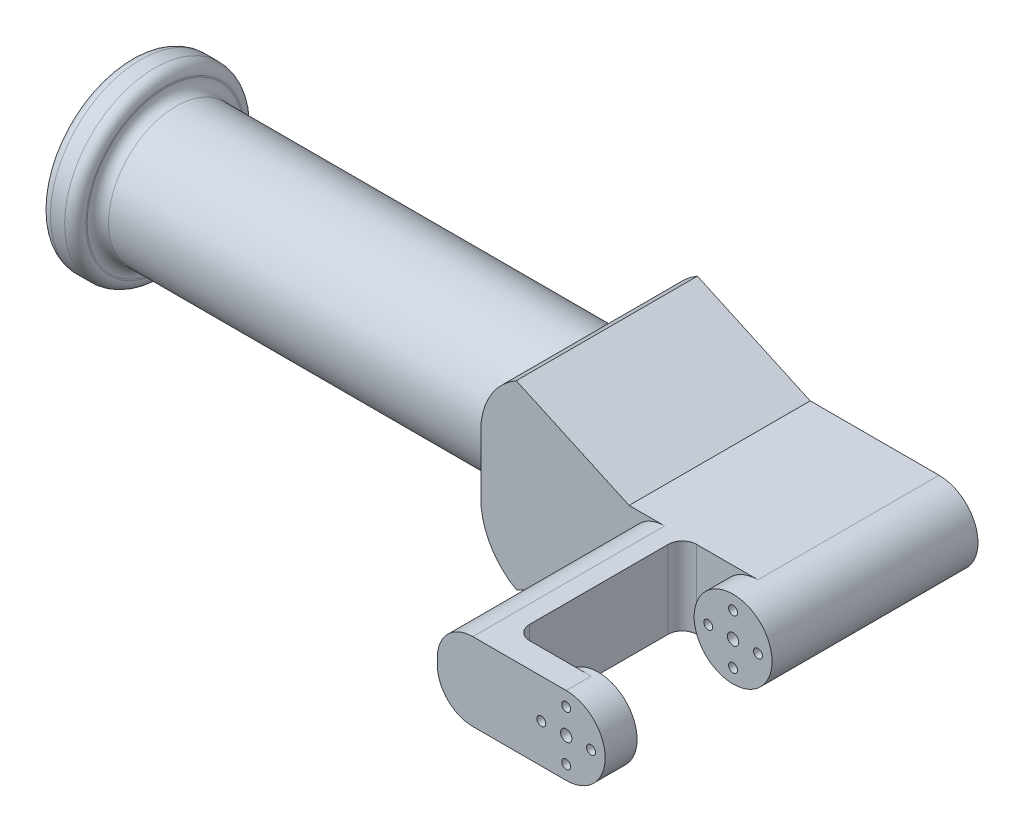
SolidWorks part; units mm, degrees
material "PET"
ref_plane "Front Plane" through (0, 0, 0) normal (0, 0, 1) x (1, 0, 0)
ref_plane "Top Plane" through (0, 0, 0) normal (0, 1, 0) x (1, 0, 0)
ref_plane "Right Plane" through (0, 0, 0) normal (1, 0, 0) x (0, 0, -1)
sketch "Sketch1" plane through (0, 0, 0) normal (1, 0, 0) x (0, 0, -1)
  line L0 (0, 10.97) -> (80, 10.97)
  line L1 (80, 10.97) -> (80, -10.97)
  line L2 (0, -10.97) -> (80, -10.97)
  arc A0 (0, 10.97) -> (0, -10.97) centre (0, 0) ccw
  dimension "D1" = 21.94
  dimension "D2" = 80
extrude "Boss-Extrude1" add sketch "Sketch1" along normal blind 15
sketch "Sketch2" plane through (15, 0, 0) normal (1, 0, 0) x (0, 0, -1)
  line L0 (0, 28.05) -> (0, -28.05) construction
  circle A0 centre (0, 0) radius 10.97
  circle A1 centre (0, 0) radius 1.6
  circle A2 centre (0, 6.58) radius 1.25
  circle A3 centre (6.58, 0) radius 1.25
  circle A4 centre (0, -6.58) radius 1.25
  circle A5 centre (-6.58, 0) radius 1.25
  point P17 (0, 0)
  dimension "D1" = 3.2
  dimension "D2" = 2.5
  dimension "D3" = 6.58
  dimension "D4" = 4
extrude "Boss-Extrude2" add sketch "Sketch2" along normal blind 5.89
sketch "Sketch3" plane through (20.89, 0, 0) normal (1, 0, 0) x (0, 0, -1)
  circle A0 centre (0, 6.58) radius 1.25
  circle A1 centre (0, 0) radius 1.6
  circle A2 centre (0, -6.58) radius 1.25
  circle A3 centre (-6.58, 0) radius 1.25
  circle A4 centre (6.58, 0) radius 1.25
extrude "Cut-Extrude1" cut sketch "Sketch3" against normal blind 100
sketch "Sketch4" plane through (15, 0, 0) normal (1, 0, 0) x (0, 0, -1)
  line L0 (80, 10.97) -> (0, 10.97) construction
  line L1 (30, 10.97) -> (80, 10.97)
  line L2 (30, 10.97) -> (30, -10.97)
  line L3 (30, -10.97) -> (80, -10.97)
  line L4 (80, 10.97) -> (80, -10.97)
  dimension "D1" = 30
extrude "Boss-Extrude3" add sketch "Sketch4" along normal blind 49.02
sketch "Sketch5" plane through (0, 0, 0) normal (0, 1, 0) x (1, 0, 0)
  line L0 (0, -12.067) -> (0, 12.067) construction
  line L1 (64.02, 34.7595) -> (0, 34.7595) construction
  line L2 (64.02, 80) -> (64.02, 30) construction
  line L3 (32.01, 80) -> (32.01, -10.8477) construction
  line L4 (64.02, 80) -> (0, 80) construction
sketch "Sketch6" plane through (0, 10.97, 0) normal (0, 1, 0) x (1, 0, 0)
  line L0 (64.02, 80) -> (0, 80) construction
  line L1 (15, 30) -> (44, 30)
  line L2 (15, 30) -> (15, 80)
  line L3 (15, 80) -> (44, 80)
  line L4 (44, 30) -> (44, 80)
sketch "Sketch9" plane through (0, 0, 0) normal (-1, 0, 0) x (0, 0, 1)
  line L0 (-80, 0) -> (10.8477, 0) construction
  line L1 (-80, 25.5) -> (-29, 25.5)
  line L2 (-80, 25.5) -> (-80, -25.5)
  line L3 (-80, -25.5) -> (-29, -25.5)
  line L4 (-29, 25.5) -> (-29, -25.5)
  line L5 (-80, 25.5) -> (-29, -25.5) construction
  line L6 (-80, -25.5) -> (-29, 25.5) construction
  line L7 (-80, 10.97) -> (-80, -10.97) construction
  point P0 (-54.5, 0)
  dimension "D1" = 29
  dimension "D2" = 25.5
  dimension "D3" = 0
extrude "Boss-Extrude7" add sketch "Sketch9" along normal blind 10
sketch "Sketch10" plane through (-10, 0, 0) normal (-1, 0, 0) x (0, 0, 1)
  line L0 (-80, 0) -> (-29, 0) construction
  line L1 (-80, 10.97) -> (-80, -10.97) construction
  line L2 (-29, -25.5) -> (-29, 25.5) construction
  circle A0 centre (-54.5, 0) radius 19.05
  dimension "D1" = 38.1
extrude "Boss-Extrude8" add sketch "Sketch10" along normal blind 114.3
sketch "Sketch11" plane through (-124.3, 0, 0) normal (-1, 0, 0) x (0, 0, 1)
  line L0 (-73.55, 0) -> (-35.45, 0) construction
  line L1 (-80, 0) -> (10.8477, 0) construction
  circle A0 centre (-54.5, 0) radius 19.05 construction
  circle A1 centre (-54.5, 0) radius 25.4
  dimension "D1" = 50.8
extrude "Boss-Extrude9" add sketch "Sketch11" along normal blind 10
sketch "Sketch12" plane through (0, 0, -30) normal (0, 0, 1) x (1, 0, 0)
  line L0 (64.02, -10.97) -> (15, -10.97) construction
  line L1 (64.02, 10.97) -> (49.02, 10.97)
  line L2 (64.02, 10.97) -> (64.02, -10.97)
  line L3 (64.02, -10.97) -> (49.02, -10.97)
  line L4 (49.02, 10.97) -> (49.02, -10.97)
  dimension "D1" = 15
extrude "Boss-Extrude10" add sketch "Sketch12" along normal blind 30
sketch "Sketch13" plane through (64.02, 0, 0) normal (1, 0, 0) x (0, 0, -1)
  circle A0 centre (0, 0) radius 10.97
  circle A1 centre (0, 0) radius 1.6
  circle A2 centre (6.58, 0) radius 1.25
  circle A3 centre (0, 6.58) radius 1.25
  circle A4 centre (0, -6.58) radius 1.25
  circle A5 centre (-6.58, 0) radius 1.25
  point P17 (0, 0)
  dimension "D1" = 4
extrude "Boss-Extrude11" add sketch "Sketch13" against normal blind 20.89
sketch "Sketch15" plane through (64.02, 0, 0) normal (1, 0, 0) x (0, 0, -1)
  circle A0 centre (0, 0) radius 1.6
  circle A1 centre (0, 6.58) radius 1.25
  circle A2 centre (6.58, 0) radius 1.25
  circle A3 centre (0, -6.58) radius 1.25
  circle A4 centre (-6.58, 0) radius 1.25
  point P15 (0, 0)
  dimension "D1" = 4
extrude "Cut-Extrude2" cut sketch "Sketch15" against normal blind 20.89
sketch "Sketch17" plane through (0, 0, 0) normal (1, 0, 0) x (0, 0, -1)
  line L1 (29, 25.5) -> (80, 25.5)
  line L2 (29, 25.5) -> (29, -25.5)
  line L3 (29, -25.5) -> (80, -25.5)
  line L4 (80, 25.5) -> (80, -25.5)
extrude "Boss-Extrude12" add sketch "Sketch17" along normal blind 79.02
sketch "Sketch18" plane through (0, 0, -29) normal (0, 0, 1) x (1, 0, 0)
  line L1 (39.5513, 13.4042) -> (70.044, 13.4042)
  line L2 (39.5513, 13.4042) -> (39.5513, -17.0884)
  line L3 (39.5513, -17.0884) -> (70.044, -17.0884)
  line L4 (70.044, 13.4042) -> (70.044, -17.0884)
extrude "Cut-Extrude3" cut sketch "Sketch18" along normal blind 64
sketch "Sketch19" plane through (0, 0, -29) normal (0, 0, 1) x (1, 0, 0)
  line L0 (79.02, 25.5) -> (79.02, -25.5) construction
  line L1 (79.02, 10.97) -> (64.02, 10.97)
  line L2 (79.02, 10.97) -> (79.02, -10.97)
  line L3 (79.02, -10.97) -> (64.02, -10.97)
  line L4 (64.02, 10.97) -> (64.02, -10.97)
  line L5 (50.0335, 0) -> (-50.0335, 0) construction
  dimension "D1" = 15
  dimension "D2" = 21.94
  dimension "D3" = 10.97
extrude "Boss-Extrude13" add sketch "Sketch19" along normal blind 29
sketch "Sketch20" plane through (79.02, 0, 0) normal (1, 0, 0) x (0, 0, -1)
  circle A0 centre (0, 0) radius 10.97
  circle A1 centre (0, 0) radius 1.6
  circle A2 centre (0, 6.58) radius 1.25
  circle A3 centre (6.58, 0) radius 1.25
  circle A4 centre (0, -6.58) radius 1.25
  circle A5 centre (-6.58, 0) radius 1.25
  point P17 (0, 0)
  dimension "D1" = 4
extrude "Boss-Extrude14" add sketch "Sketch20" against normal blind 20.98
sketch "Sketch21" plane through (79.02, 0, 0) normal (1, 0, 0) x (0, 0, -1)
  circle A0 centre (0, 0) radius 1.6
  circle A1 centre (0, 6.58) radius 1.25
  circle A2 centre (6.58, 0) radius 1.25
  circle A3 centre (0, -6.58) radius 1.25
  circle A4 centre (-6.58, 0) radius 1.25
  point P14 (0, 0)
  dimension "D1" = 4
extrude "Cut-Extrude4" cut sketch "Sketch21" against normal blind 20.98
sketch "Sketch23" plane through (79.02, 0, 0) normal (1, 0, 0) x (0, 0, -1)
  line L0 (29, -10.97) -> (29, -25.5) construction
  line L1 (-13.4821, 15.5896) -> (29, 15.5896)
  line L2 (-13.4821, 15.5896) -> (-13.4821, -18.235)
  line L3 (-13.4821, -18.235) -> (29, -18.235)
  line L4 (29, 15.5896) -> (29, -18.235)
extrude "Cut-Extrude6" cut sketch "Sketch23" against normal blind 100
sketch "Sketch27" plane through (0, 0, -29) normal (0, 0, 1) x (1, 0, 0)
  line L1 (44, 0) -> (-44, 0) construction
  line L2 (25.67, 18.75) -> (52.37, 18.75)
  line L3 (25.67, 18.75) -> (25.67, -18.75)
  line L4 (25.67, -18.75) -> (52.37, -18.75)
  line L5 (52.37, 18.75) -> (52.37, -18.75)
  line L6 (25.67, 18.75) -> (52.37, -18.75) construction
  line L7 (25.67, -18.75) -> (52.37, 18.75) construction
  line L8 (79.02, 25.5) -> (79.02, -25.5) construction
  point P2 (39.02, 0)
  dimension "D1" = 26.7
  dimension "D2" = 37.5
  dimension "D3" = 40
sketch "Sketch24" plane through (0, 25.5, 0) normal (0, 1, 0) x (1, 0, 0)
  line L0 (-10, 54.5) -> (79.02, 54.5) construction
  line L1 (-10, 29) -> (-10, 80) construction
  line L2 (79.02, 80) -> (79.02, 29) construction
  circle A0 centre (34.51, 54.5) radius 1.6
  circle A1 centre (34.51, 61.08) radius 1.25
  circle A2 centre (41.09, 54.5) radius 1.25
  circle A3 centre (34.51, 47.92) radius 1.25
  circle A4 centre (27.93, 54.5) radius 1.25
  dimension "D1" = 3.2
  dimension "D2" = 2.5
  dimension "D3" = 6.58
  dimension "D4" = 4
sketch "Sketch31" plane through (0, 25.5, 0) normal (0, 1, 0) x (1, 0, 0)
  line L0 (-28.05, 0) -> (28.05, 0) construction
  line L1 (-10, 80) -> (40.8, 80)
  line L2 (-10, 80) -> (-10, 0)
  line L3 (-10, 0) -> (40.8, 0)
  line L4 (40.8, 80) -> (40.8, 0)
  dimension "D1" = 50.8
sketch "Sketch32" plane through (0, 25.5, 0) normal (0, 1, 0) x (1, 0, 0)
  line L0 (-10, 80) -> (79.02, 80) construction
  line L1 (79.02, 29) -> (40.8, 29)
  line L2 (79.02, 29) -> (79.02, 80)
  line L3 (79.02, 80) -> (40.8, 80)
  line L4 (40.8, 29) -> (40.8, 80)
sketch "Sketch38" plane through (-10, 0, 0) normal (-1, 0, 0) x (0, 0, 1)
  line L0 (-80, -25.5) -> (-10.8, -25.5) construction
  line L5 (-80, 25.5) -> (-53.9876, 25.5)
  line L6 (-80, 25.5) -> (-80, -25.5)
  line L7 (-80, -25.5) -> (-53.9876, -25.5)
  line L8 (-53.9876, 25.5) -> (-53.9876, -25.5)
  circle A2 centre (-53.9876, 0) radius 25.5
fillet "Fillet6" radius 3 2 edges at (-124.3, 0, -29.1) (-124.3, 0, -35.45)
fillet "Fillet7" radius 3 1 edges at (-134.3, 0, -29.1)
sketch "Sketch40" plane through (0, 25.5, 0) normal (0, 1, 0) x (1, 0, 0)
  line L0 (0, -28.05) -> (0, 28.05) construction
  line L1 (79.02, 80) -> (0, 80)
  line L2 (79.02, 80) -> (79.02, 39)
  line L3 (79.02, 39) -> (0, 39)
  line L4 (0, 80) -> (0, 39)
  line L6 (79.02, 29) -> (40.8, 29) construction
  dimension "D1" = 10
sketch "Sketch41" plane through (0, 0, -29) normal (0, 0, 1) x (1, 0, 0)
  line L0 (28.05, 0) -> (-28.05, 0) construction
  line L1 (79.02, 25.5) -> (79.02, -25.5) construction
  line L2 (0, -28.05) -> (0, 28.05) construction
  line L3 (-10, 25.5) -> (79.02, 25.5)
  line L4 (-10, 25.5) -> (-10, -25.5)
  line L5 (-10, -25.5) -> (79.02, -25.5)
  line L6 (79.02, 25.5) -> (79.02, -25.5)
  line L7 (0, 25.5) -> (79.02, 25.5)
  line L8 (0, 25.5) -> (0, -25.5)
  line L9 (0, -25.5) -> (79.02, -25.5)
  line L10 (79.02, 25.5) -> (79.02, -25.5)
  line L11 (0, -25.5) -> (31.7741, -10.97)
  line L12 (0, 25.5) -> (31.7741, 10.97)
  line L13 (68.05, 10.97) -> (31.7741, 10.97)
  line L15 (31.7741, -10.97) -> (68.05, -10.97)
  circle A0 centre (68.05, 0) radius 10.97
  line M11 (79.02, -25.5) -> (79.02, 25.5)
  line M12 (79.02, 25.5) -> (-10, 25.5)
  dimension "D1" = 21.94
  dimension "D2" = 10.97
extrude "Cut-Extrude16" cut sketch "Sketch41" against normal blind 100 contours A0 L15 L11 L5 M11 | A0 L10 L12 L13 M12 region at (47.6027, 18.5617, -29) region at (47.6027, -18.5617, -29)
fillet "Fillet9" radius 20 1 edges at (-10, 25.5, -54.5)
fillet "Fillet10" radius 20 1 edges at (-10, -25.5, -54.5)
sketch "Sketch45" plane through (0, 0, -29) normal (0, 0, 1) x (1, 0, 0)
  line L0 (31.7741, 10.97) -> (31.7741, -10.97)
  line L1 (31.7741, -10.97) -> (46.7741, -10.97)
  line L2 (31.7741, -10.97) -> (68.05, -10.97) construction
  line L3 (46.7741, -10.97) -> (46.7741, 10.97)
  line L4 (68.05, 10.97) -> (31.7741, 10.97) construction
  line L5 (46.7741, 10.97) -> (31.7741, 10.97)
  dimension "D1" = 15
extrude "Boss-Extrude19" add sketch "Sketch45" along normal blind 54
sketch "Sketch46" plane through (46.7741, 0, 0) normal (1, 0, 0) x (0, 0, -1)
  line L0 (-25, -10.97) -> (29, -10.97) construction
  line L1 (-25, 10.97) -> (-18, 10.97)
  line L2 (-25, 10.97) -> (-25, -10.97)
  line L3 (-25, -10.97) -> (-18, -10.97)
  line L4 (-18, 10.97) -> (-18, -10.97)
  dimension "D1" = 7
extrude "Boss-Extrude20" add sketch "Sketch46" along normal up to vertex (21.2759 mm away) up to point (68.05, 10.97, -29)
sketch "Sketch47" plane through (0, 0, 18) normal (0, 0, -1) x (-1, 0, 0)
  line L0 (-68.05, -10.97) -> (-68.05, 10.97) construction
  circle A0 centre (-68.05, 0) radius 10.97
  dimension "D1" = 21.94
extrude "Boss-Extrude21" add sketch "Sketch47" along normal blind 2 and the other way up to surface (7 mm away) other way up to face at (49.9121, 0, 25)
fillet "Fillet11" radius 10 2 edges at (31.7741, -10.97, -2) (31.7741, 10.97, -2)
fillet "Fillet12" radius 4 2 edges at (46.7741, 0, 18) (46.7741, 0, -29)
sketch "Sketch50" plane through (0, 0, -29) normal (0, 0, 1) x (1, 0, 0)
  circle A0 centre (68.05, 0) radius 10.97
extrude "Boss-Extrude22" add sketch "Sketch50" along normal blind 7
sketch "Sketch51" plane through (0, 0, -22) normal (0, 0, 1) x (1, 0, 0)
  line L0 (68.05, 0) -> (68.05, 7) construction
  circle A0 centre (68.05, 0) radius 1.6
  circle A1 centre (68.05, 7) radius 1.25
  circle A2 centre (75.05, 0) radius 1.25
  circle A3 centre (68.05, -7) radius 1.25
  circle A4 centre (61.05, 0) radius 1.25
  dimension "D1" = 3.2
  dimension "D3" = 2.5
  dimension "D4" = 4
  dimension "D2" = 7
extrude "Cut-Extrude18" cut sketch "Sketch51" against normal through all both and the other way through all
